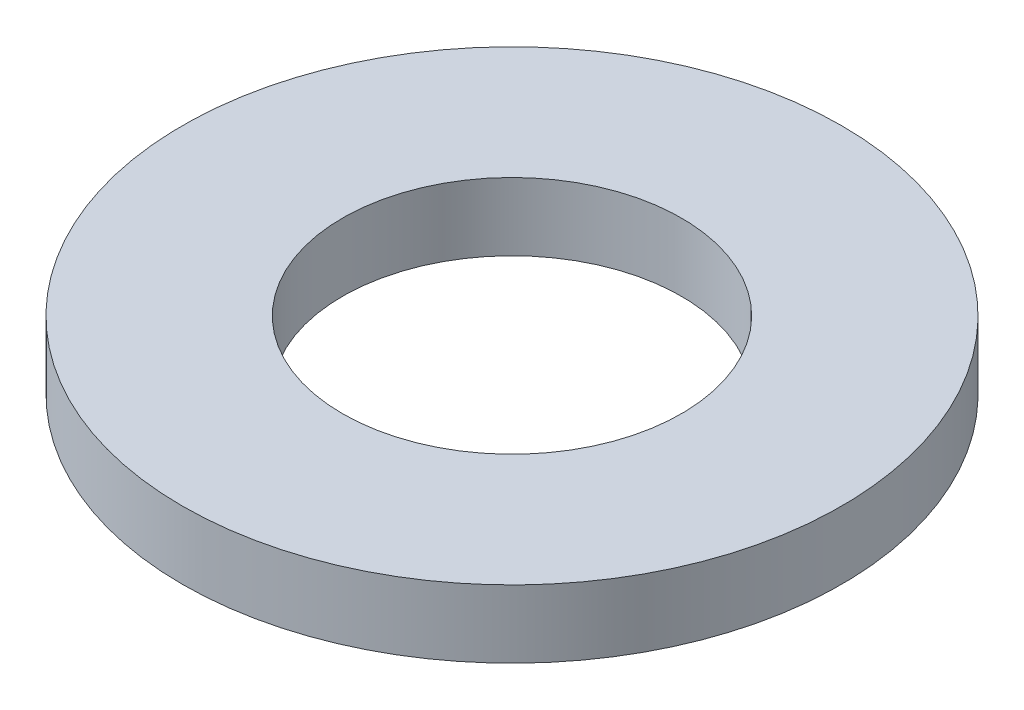
SolidWorks part; units mm, degrees
ref_plane "Front Plane" through (0, 0, 0) normal (0, 0, 1) x (1, 0, 0)
ref_plane "Top Plane" through (0, 0, 0) normal (0, 1, 0) x (1, 0, 0)
ref_plane "Right Plane" through (0, 0, 0) normal (1, 0, 0) x (0, 0, -1)
sketch "Sketch1" plane through (0, 0, 0) normal (0, 1, 0) x (1, 0, 0)
  circle A0 centre (0, 0) radius 87.5
  dimension "FLANGE_OD" = 175
extrude "Boss-Extrude1" add sketch "Sketch1" along normal blind 18
sketch "Sketch2" plane through (0, 0, 0) normal (0, 1, 0) x (1, 0, 0)
  circle A0 centre (0, 0) radius 45
  dimension "BORE_D" = 90
extrude "Cut-Extrude1" cut sketch "Sketch2" along normal through all
sketch "Sketch3" plane through (0, 18, 0) normal (0, 1, 0) x (1, 0, 0)
  circle A0 centre (0, 0) radius 36.7793 construction
  circle A1 centre (-36.7793, 0) radius 6.7345
  dimension "BOLT_D" = 13.469
  dimension "BOLT_PCD" = 73.5585
extrude "Cut-Extrude2" cut sketch "Sketch3" against normal blind 11.4093 rebuild error yes
pattern_circular "CirPattern1" count 6 over 360 rebuild error yes
